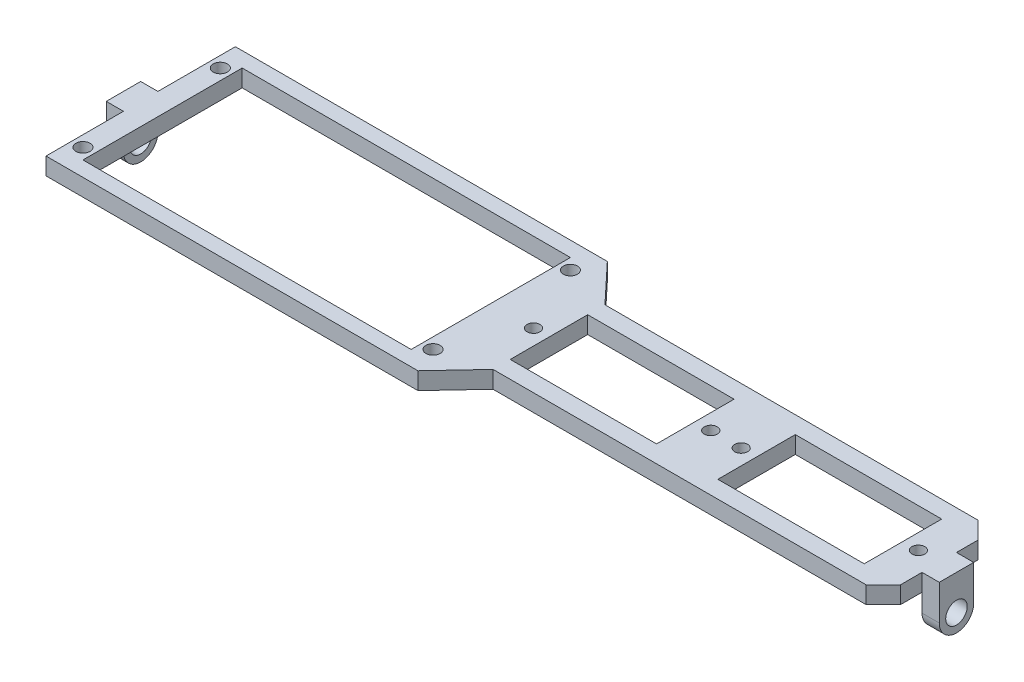
SolidWorks part; units mm, degrees
ref_plane "Plan de face" through (0, 0, 0) normal (0, 0, 1) x (1, 0, 0)
ref_plane "Plan de dessus" through (0, 0, 0) normal (0, 1, 0) x (1, 0, 0)
ref_plane "Plan de droite" through (0, 0, 0) normal (1, 0, 0) x (0, 0, -1)
sketch "Esquisse1" plane through (0, 0, 0) normal (0, 1, 0) x (1, 0, 0)
  line L0 (9.6088, 14.324) -> (9.6088, -7.676) construction
  line L1 (-11.9962, 14.324) -> (31.2138, 14.324)
  line L2 (-11.9962, 14.324) -> (-11.9962, -7.676)
  line L3 (-11.9962, -7.676) -> (31.2138, -7.676)
  line L4 (31.2138, 14.324) -> (31.2138, -7.676)
  line L5 (-11.9962, 5.324) -> (-13.9962, 5.324)
  line L6 (-11.9962, 5.324) -> (-11.9962, 1.324)
  line L7 (-11.9962, 1.324) -> (-13.9962, 1.324)
  line L8 (-13.9962, 5.324) -> (-13.9962, 1.324)
  line L9 (-9.4562, 3.324) -> (28.6738, 3.324) construction
  line L10 (28.6738, -5.926) -> (-9.4562, -5.926)
  line L11 (28.6738, -5.926) -> (28.6738, 12.574)
  line L12 (28.6738, 12.574) -> (-9.4562, 12.574)
  line L13 (-9.4562, -5.926) -> (-9.4562, 12.574)
  line L14 (28.6738, -5.926) -> (-9.4562, 12.574) construction
  line L15 (28.6738, 12.574) -> (-9.4562, -5.926) construction
  line L16 (35.4338, -3.176) -> (80.7738, -3.176)
  line L17 (52.4338, -1.176) -> (35.4338, -1.176)
  line L18 (52.4338, -1.176) -> (52.4338, 7.824)
  line L19 (52.4338, 7.824) -> (35.4338, 7.824)
  line L20 (35.4338, -1.176) -> (35.4338, 7.824)
  line L21 (52.4338, -1.176) -> (35.4338, 7.824) construction
  line L22 (52.4338, 7.824) -> (35.4338, -1.176) construction
  line L23 (35.4338, 9.824) -> (80.7738, 9.824)
  line L24 (31.2138, -7.676) -> (35.4338, -3.176)
  line L25 (31.2138, 14.324) -> (35.4338, 9.824)
  line L26 (43.9338, 7.824) -> (43.9338, -1.176) construction
  line L27 (55.9938, 9.824) -> (55.9938, -3.176) construction
  line L32 (59.5538, 7.824) -> (76.5538, 7.824)
  line L33 (76.5538, -1.176) -> (76.5538, 7.824)
  line L34 (59.5538, -1.176) -> (76.5538, -1.176)
  line L35 (59.5538, -1.176) -> (59.5538, 7.824)
  line L36 (80.7738, 9.824) -> (80.7738, -3.176)
  line L38 (80.7738, 5.324) -> (82.7738, 5.324)
  line L39 (80.7738, 5.324) -> (80.7738, 1.324)
  line L40 (80.7738, 1.324) -> (82.7738, 1.324)
  line L41 (82.7738, 5.324) -> (82.7738, 1.324)
  circle A0 centre (-10.7262, 11.304) radius 0.825
  circle A1 centre (29.9438, 11.304) radius 0.825
  circle A2 centre (29.9438, -4.656) radius 0.825
  circle A3 centre (-10.7262, -4.656) radius 0.825
  circle A4 centre (33.6388, 3.324) radius 0.75
  circle A5 centre (54.2288, 3.324) radius 0.75
  circle A6 centre (57.7588, 3.324) radius 0.75
  circle A7 centre (78.3488, 3.324) radius 0.75
  point P8 (-13.9962, 3.324)
  point P9 (-11.9962, 3.324)
  point P12 (9.6088, 3.324)
  point P13 (9.6088, 3.324)
  point P28 (43.9338, 3.324)
  point P39 (33.6388, 3.324)
  point P58 (80.7738, 3.324)
  point P59 (82.7738, 3.324)
  dimension "D8" = 1.65
  dimension "D16" = 1.5
  dimension "D1" = 22
  dimension "D2" = 43.21
  dimension "D3" = 4
  dimension "D4" = 2
  dimension "D5" = 2.54
  dimension "D6" = 2.54
  dimension "D7" = 18.5
  dimension "D9" = 1.27
  dimension "D10" = 1.27
  dimension "D11" = 17
  dimension "D12" = 9
  dimension "D13" = 4.22
  dimension "D14" = 2
  dimension "D15" = 2
  dimension "D17" = 49.56
  dimension "D18" = 24.78
  dimension "D19" = 4
  dimension "D20" = 2
  dimension "D21" = 10.295
extrude "Boss.-Extru.1" add sketch "Esquisse1" along normal blind 2 contours L4 L1 L2 L3 A1 A0 L10 L13 L12 L11 A2 A3 | L36 L23 L25 L4 L24 L16 A5 A4 L17 L20 L19 L18 L34 L35 L32 L33 A6 A7 | L41 L38 L36 L40 | L5 L8 L7 L2 region at (9.6088, 0, -13.8391) region at (32.9283, 0, -11.7031) region at (-12.9962, 0, -3.324) region at (81.7738, 0, -3.324)
chamfer "Chanfrein1" distance 2 angle 45 2 edges at (80.7738, 1, 3.176) (80.7738, 1, -9.824)
sketch "Esquisse2" plane through (82.7738, 0, 0) normal (1, 0, 0) x (0, 0, -1)
  line L1 (1.324, 0) -> (5.324, 0)
  line L2 (1.324, 0) -> (1.324, -4.1)
  line L3 (1.324, -4.1) -> (5.324, -4.1)
  line L4 (5.324, 0) -> (5.324, -4.1)
  line L6 (1.324, -2.05) -> (5.324, -2.05) construction
  circle A0 centre (3.324, -2.05) radius 1.25
  point P7 (3.324, -0.8)
  point P8 (3.324, -3.3)
  point P13 (3.324, -2.05)
  dimension "D2" = 2.5
  dimension "D1" = 0.8
extrude "Boss.-Extru.2" add sketch "Esquisse2" against normal blind 2
fillet "Congé1" radius 2 2 edges at (81.7738, -4.1, -5.324) (81.7738, -4.1, -1.324)
sketch "Esquisse4" plane through (-13.9962, 0, 0) normal (-1, 0, 0) x (0, 0, 1)
  line L0 (-5.324, -2.05) -> (-1.324, -2.05) construction
  line L1 (-5.324, 0) -> (-1.324, 0)
  line L2 (-5.324, 0) -> (-5.324, -4.1)
  line L3 (-5.324, -4.1) -> (-1.324, -4.1)
  line L4 (-1.324, 0) -> (-1.324, -4.1)
  circle A0 centre (-3.324, -2.05) radius 1.25
  point P10 (-3.324, -3.3)
  point P11 (-3.324, -4.1)
  dimension "D1" = 2.5
  dimension "D2" = 0.8
extrude "Boss.-Extru.3" add sketch "Esquisse4" against normal blind 2
fillet "Congé2" radius 2 2 edges at (-12.9962, -4.1, -5.324) (-12.9962, -4.1, -1.324)
